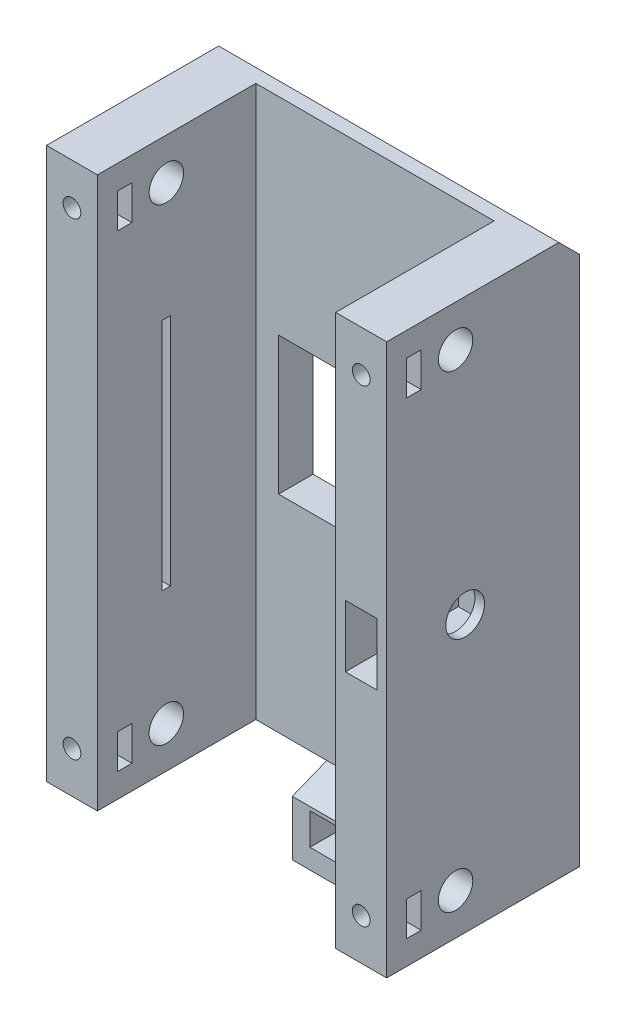
SolidWorks part; units mm, degrees
ref_plane "Front Plane" through (0, 0, 0) normal (0, 0, 1) x (1, 0, 0)
ref_plane "Top Plane" through (0, 0, 0) normal (0, 1, 0) x (1, 0, 0)
ref_plane "Right Plane" through (0, 0, 0) normal (1, 0, 0) x (0, 0, -1)
sketch "Sketch1" plane through (0, 0, 0) normal (0, 0, 1) x (1, 0, 0)
  line L1 (-57.15, -63.5) -> (57.15, -63.5)
  line L2 (-57.15, -63.5) -> (-57.15, 63.5)
  line L3 (-57.15, 63.5) -> (57.15, 63.5)
  line L4 (57.15, -63.5) -> (57.15, 63.5)
  line L5 (-57.15, -63.5) -> (57.15, 63.5) construction
  line L6 (-57.15, 63.5) -> (57.15, -63.5) construction
  point P0 (0, 0)
  dimension "D1" = 114.3
  dimension "D2" = 127
extrude "Boss-Extrude1" add sketch "Sketch1" along normal blind 6.35
ref_plane "Plane1" through (0, 0, 0) normal (1, 0, 0) x (0, 0, -1)
ref_plane "Plane2" through (0, 0, 0) normal (0, 1, 0) x (1, 0, 0)
sketch "Sketch2" plane through (0, 0, 6.35) normal (0, 0, 1) x (1, 0, 0)
  line L1 (21.971, -50.8) -> (31.369, -50.8)
  line L2 (21.971, -50.8) -> (21.971, 50.8)
  line L3 (21.971, 50.8) -> (31.369, 50.8)
  line L4 (31.369, -50.8) -> (31.369, 50.8)
  line L5 (21.971, -50.8) -> (31.369, 50.8) construction
  line L6 (21.971, 50.8) -> (31.369, -50.8) construction
  point P0 (26.67, 0)
  dimension "D1" = 26.67
  dimension "D2" = 101.6
  dimension "D3" = 9.398
extrude "Boss-Extrude2" add sketch "Sketch2" along normal blind 29.21
mirror "Mirror1" about plane through (0, 0, 0) normal (1, 0, 0) of "Boss-Extrude2"
sketch "Sketch10" plane through (31.369, 0, 0) normal (1, 0, 0) x (0, 0, -1)
  line L0 (-35.56, 50.8) -> (-6.35, 50.8) construction
  line L3 (-6.35, -50.8) -> (-6.35, 50.8) construction
  circle A0 centre (-22.86, 43.18) radius 3.175
  dimension "D1" = 6.35
  dimension "D2" = 7.62
  dimension "D3" = 16.51
extrude "Cut-Extrude1" cut sketch "Sketch10" against normal through all
mirror "Mirror2" about plane through (0, 0, 0) normal (0, 1, 0) of "Cut-Extrude1"
sketch "Sketch13" plane through (31.369, 0, 0) normal (1, 0, 0) x (0, 0, -1)
  line L0 (-35.56, 50.8) -> (-6.35, 50.8) construction
  line L1 (-31.877, 40.005) -> (-29.21, 40.005)
  line L2 (-31.877, 40.005) -> (-31.877, 46.355)
  line L3 (-31.877, 46.355) -> (-29.21, 46.355)
  line L4 (-29.21, 40.005) -> (-29.21, 46.355)
  line L5 (-31.877, 40.005) -> (-29.21, 46.355) construction
  line L6 (-31.877, 46.355) -> (-29.21, 40.005) construction
  circle A0 centre (-22.86, 43.18) radius 3.175 construction
  point P0 (-30.5435, 43.18)
  dimension "D1" = 2.667
  dimension "D2" = 6.35
  dimension "D3" = 7.62
  dimension "D4" = 6.35
extrude "Cut-Extrude2" cut sketch "Sketch13" against normal up to surface (9.398 mm away) up to face at (21.971, 0, 20.955)
sketch "Sketch15" plane through (0, 0, 6.35) normal (0, 0, 1) x (1, 0, 0)
  line L1 (-17.78, -12.7) -> (7.62, -12.7)
  line L2 (-17.78, -12.7) -> (-17.78, 12.7)
  line L3 (-17.78, 12.7) -> (7.62, 12.7)
  line L4 (7.62, -12.7) -> (7.62, 12.7)
  line L5 (-17.78, -12.7) -> (7.62, 12.7) construction
  line L6 (-17.78, 12.7) -> (7.62, -12.7) construction
  line L7 (0, -3.4925) -> (0, 3.4925) construction
  point P0 (-5.08, 0)
  dimension "D1" = 25.4
  dimension "D2" = 25.4
  dimension "D3" = 5.08
extrude "Cut-Extrude3" cut sketch "Sketch15" against normal up to next
hole_wizard "#4 Clearance Hole1" positions "Sketch17" profile "Sketch16" hole size "#4" standard "ANSI Inch"
sketch "Sketch17" plane through (0, 0, 35.56) normal (0, 0, 1) x (1, 0, 0)
  line L0 (31.369, 50.8) -> (21.971, 50.8) construction
  line L1 (31.369, -50.8) -> (31.369, 50.8) construction
  point P0 (26.67, 43.18)
  dimension "D1" = 7.62
  dimension "D2" = 4.699
sketch "Sketch16" plane through (26.67, 43.18, 35.56) normal (1, 0, 0) x (0, -1, 0)
  line L0 (0, 0) -> (0, 12.9186)
  line L1 (0, 12.9186) -> (1.6319, 11.938)
  line L2 (1.6319, 11.938) -> (1.6319, 0)
  line L5 (1.6319, 0) -> (0, 0)
  line L10 (0, 12.9186) -> (-1.632, 11.938) construction
  line L11 (0, -6.35) -> (0, 107.95) construction
  dimension "Hole Dia." = 3.2639
  dimension "Hole Depth" = 11.938
  dimension "Drill Angle" = 118
mirror "Mirror3" about plane through (0, 0, 0) normal (1, 0, 0) of "#4 Clearance Hole1", "Cut-Extrude2"
mirror "Mirror4" about plane through (0, 0, 0) normal (0, 1, 0) of "Mirror3"
sketch "Sketch19" plane through (-21.971, 0, 0) normal (1, 0, 0) x (0, 0, -1)
  line L0 (3.4925, 0) -> (-3.4925, 0) construction
  line L1 (-23.622, -21.59) -> (-22.098, -21.59)
  line L2 (-23.622, -21.59) -> (-23.622, 21.59)
  line L3 (-23.622, 21.59) -> (-22.098, 21.59)
  line L4 (-22.098, -21.59) -> (-22.098, 21.59)
  line L5 (-23.622, -21.59) -> (-22.098, 21.59) construction
  line L6 (-23.622, 21.59) -> (-22.098, -21.59) construction
  line L7 (-35.56, -50.8) -> (-35.56, 50.8) construction
  point P0 (-22.86, 0)
  dimension "D1" = 43.18
  dimension "D2" = 1.524
  dimension "D3" = 12.7
extrude "Cut-Extrude4" cut sketch "Sketch19" against normal blind 5.08
sketch "Sketch23" plane through (0, 0, 35.56) normal (0, 0, 1) x (1, 0, 0)
  line L0 (55, 0) -> (-55, 0) construction
  line L1 (23.749, -5.715) -> (29.591, -5.715)
  line L2 (23.749, -5.715) -> (23.749, 5.715)
  line L3 (23.749, 5.715) -> (29.591, 5.715)
  line L4 (29.591, -5.715) -> (29.591, 5.715)
  line L5 (23.749, -5.715) -> (29.591, 5.715) construction
  line L6 (23.749, 5.715) -> (29.591, -5.715) construction
  line L7 (31.369, -50.8) -> (31.369, 50.8) construction
  point P0 (26.67, 0)
  dimension "D1" = 5.842
  dimension "D2" = 11.43
  dimension "D3" = 4.699
extrude "Cut-Extrude5" cut sketch "Sketch23" against normal blind 20.828
sketch "Sketch24" plane through (0, 63.5, 0) normal (0, 1, 0) x (1, 0, 0)
  line L1 (-63.9407, 4.6677) -> (63.9407, 4.6677)
  line L2 (-63.9407, 4.6677) -> (-63.9407, -11.5225)
  line L3 (-63.9407, -11.5225) -> (63.9407, -11.5225)
  line L4 (63.9407, 4.6677) -> (63.9407, -11.5225)
  line L5 (-63.9407, 4.6677) -> (63.9407, -11.5225) construction
  line L6 (-63.9407, -11.5225) -> (63.9407, 4.6677) construction
  point P0 (0, -3.4274)
extrude "Cut-Extrude6" cut sketch "Sketch24" against normal blind 12.7
mirror "Mirror5" about plane through (0, 0, 0) normal (0, 1, 0) of "Cut-Extrude6"
sketch "Sketch26" plane through (57.15, 0, 0) normal (1, 0, 0) x (0, 0, -1)
  line L1 (-13.5315, -55.9587) -> (6.7986, -55.9587)
  line L2 (-13.5315, -55.9587) -> (-13.5315, 55.9587)
  line L3 (-13.5315, 55.9587) -> (6.7986, 55.9587)
  line L4 (6.7986, -55.9587) -> (6.7986, 55.9587)
  line L5 (-13.5315, -55.9587) -> (6.7986, 55.9587) construction
  line L6 (-13.5315, 55.9587) -> (6.7986, -55.9587) construction
  point P0 (-3.3665, 0)
extrude "Cut-Extrude8" cut sketch "Sketch26" against normal up to vertex (25.781 mm away) up to point (31.369, 50.8, 6.35)
mirror "Mirror6" about plane through (0, 0, 0) normal (1, 0, 0) of "Cut-Extrude8"
chamfer "Chamfer1" distance 3.81 angle 45 1 edges at (0, 50.8, 0)
sketch "Sketch28" plane through (0, -50.8, 0) normal (0, -1, 0) x (1, 0, 0)
  line L0 (21.971, 6.35) -> (-21.971, 6.35) construction
  line L1 (-8.89, 0) -> (8.89, 0)
  line L2 (-8.89, 0) -> (-8.89, 12.7)
  line L3 (-8.89, 12.7) -> (8.89, 12.7)
  line L4 (8.89, 0) -> (8.89, 12.7)
  line L5 (-8.89, 0) -> (8.89, 12.7) construction
  line L6 (-8.89, 12.7) -> (8.89, 0) construction
  point P0 (0, 6.35)
  dimension "D1" = 17.78
  dimension "D2" = 12.7
extrude "Boss-Extrude3" add sketch "Sketch28" along normal blind 12.7
sketch "Sketch30" plane through (0, 0, 12.7) normal (0, 0, 1) x (1, 0, 0)
  line L1 (-5.648, -59.8632) -> (5.782, -59.8632)
  line L2 (-5.648, -59.8632) -> (-5.648, -54.0212)
  line L3 (-5.648, -54.0212) -> (5.782, -54.0212)
  line L4 (5.782, -59.8632) -> (5.782, -54.0212)
  line L5 (-5.648, -59.8632) -> (5.782, -54.0212) construction
  line L6 (-5.648, -54.0212) -> (5.782, -59.8632) construction
  point P0 (0.067, -56.9422)
  dimension "D1" = 11.43
  dimension "D2" = 5.842
extrude "Cut-Extrude9" cut sketch "Sketch30" against normal through all
hole_wizard "1/4 Clearance Hole1" positions "Sketch32" profile "Sketch31" hole size "1/4" standard "ANSI Inch" end condition up to next
sketch "Sketch32" plane through (0, -63.5, 0) normal (0, -1, 0) x (-1, 0, 0)
  line L0 (0, 55) -> (0, -55) construction
  point P0 (0, -6.35)
sketch "Sketch31" plane through (0, -63.5, 6.35) normal (1, 0, 0) x (0, 0, -1)
  line L0 (0, 0) -> (0, 3.6368)
  line L1 (0, 3.6368) -> (3.5712, 3.6368)
  line L2 (3.5712, 3.6368) -> (3.5712, 0)
  line L5 (3.5712, 0) -> (0, 0)
  line L11 (0, -6.35) -> (0, 107.95) construction
  dimension "Thru Hole Dia." = 7.1425
  dimension "Thru Hole Depth" = 3.6368
chamfer "Chamfer3" distance 6.35 distance2 2.54 1 edges at (0, -50.8, 12.7) first distance on face at (0, -50.8, 9.525)
hole_wizard "1/4 Clearance Hole2" positions "Sketch34" profile "Sketch35" hole size "1/4" standard "ANSI Inch"
sketch "Sketch34" plane through (31.369, 0, 0) normal (1, 0, 0) x (0, 0, -1)
  line L0 (55, 0) -> (-55, 0) construction
  line L1 (-14.732, -5.715) -> (-14.732, 5.715) construction
  point P0 (-21.082, 0)
  point P5 (-14.732, 0)
  dimension "D1" = 6.35
sketch "Sketch35" plane through (31.369, 0, 21.082) normal (0, 1, 0) x (0, 0, -1)
  line L0 (0, 0) -> (0, 15.24)
  line L1 (0, 15.24) -> (3.5712, 15.24)
  line L2 (3.5712, 15.24) -> (3.5712, 0)
  line L5 (3.5712, 0) -> (0, 0)
  line L10 (0, 15.24) -> (-3.5712, 15.24) construction
  line L11 (0, -6.35) -> (0, 107.95) construction
  dimension "Hole Dia." = 7.1425
  dimension "Hole Depth" = 15.24
  dimension "Drill Angle" = 180
